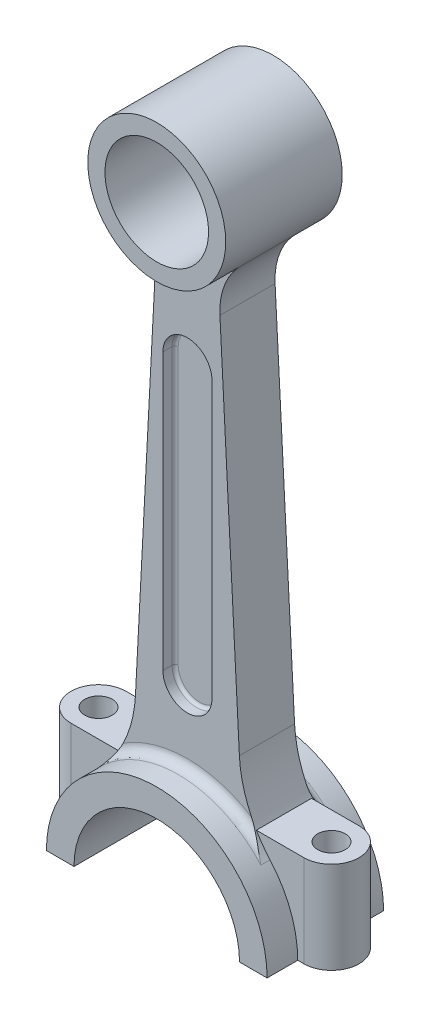
SolidWorks part; units mm, degrees
ref_plane "Front Plane" through (0, 0, 0) normal (0, 0, 1) x (1, 0, 0)
ref_plane "Top Plane" through (0, 0, 0) normal (0, 1, 0) x (1, 0, 0)
ref_plane "Right Plane" through (0, 0, 0) normal (1, 0, 0) x (0, 0, -1)
sketch "Sketch3" plane through (0, 0, 0) normal (0, 0, 1) x (1, 0, 0)
  line L0 (-10, -20.1556) -> (-17.8497, -169.9368)
  line L1 (10, -20.1556) -> (17.8497, -169.9368)
  line L2 (0, 0) -> (0, -201.2) construction
  line L3 (-36, -201.2) -> (-27, -201.2)
  line L4 (27, -201.2) -> (36, -201.2)
  circle A0 centre (0, 0) radius 22.5
  circle A1 centre (0, 0) radius 16.9
  arc A2 (36, -201.2) -> (-36, -201.2) centre (0, -201.2) ccw
  arc A3 (27, -201.2) -> (-27, -201.2) centre (0, -201.2) ccw
  dimension "D1" = 45
  dimension "D2" = 33.8
  dimension "D3" = 72
  dimension "D4" = 54
  dimension "D5" = 6
  dimension "D6" = 20
  dimension "D7" = 201.2
extrude "Boss-Extrude1" add sketch "Sketch3" along normal mid plane 38 contours A1 A0 region at (-11.5231, 18.5805, 0)
extrude "Boss-Extrude2" add sketch "Sketch3<3>" along normal mid plane 18 contours A0 L2 A2 L1 | L2 A0 L0 A2 region at (-7.1843, -100.8455, 0) region at (7.1843, -100.8455, 0)
sketch "Sketch3<3>" plane through (0, 0, 0) normal (0, 0, 1) x (1, 0, 0) same geometry as "Sketch3"
extrude "Boss-Extrude3" add sketch "Sketch3<5>" along normal mid plane 38 contours A2 L2 A3 L4 | L2 A2 L3 A3 region at (-20.1899, -181.0101, 0) region at (20.1899, -181.0101, 0)
sketch "Sketch3<5>" plane through (0, 0, 0) normal (0, 0, 1) x (1, 0, 0) same geometry as "Sketch3"
ref_plane "Plane2" through (0, -171.2, 0) normal (0, -1, 0) x (-1, 0, 0)
sketch "Sketch5" plane through (0, -171.2, 0) normal (0, -1, 0) x (-1, 0, 0)
  line L0 (38, 0) -> (-38, 0) construction
  line L1 (38, -9) -> (-38, -9)
  line L2 (38, 9) -> (-38, 9)
  arc A0 (38, -9) -> (38, 9) centre (38, 0) ccw
  arc A1 (-38, 9) -> (-38, -9) centre (-38, 0) ccw
  circle A2 centre (38, 0) radius 4.5
  circle A3 centre (-38, 0) radius 4.5
  point P2 (0, 0)
  dimension "D1" = 9
  dimension "D2" = 9
  dimension "D3" = 76
fillet "Fillet1" radius 40 2 edges at (17.8497, -169.9368, 0) (-17.8497, -169.9368, 0)
fillet "Fillet2" radius 22.5 2 edges at (10, -20.1556, 0) (-10, -20.1556, 0)
fillet "Fillet3" radius 3 2 edges at (0, -165.2, 9) (0, -165.2, -9)
extrude "Boss-Extrude5" add sketch "Sketch5" along normal blind 30
sketch "Sketch8" plane through (0, 0, -9) normal (0, 0, -1) x (-1, 0, 0)
  line L0 (-27, -201.2) -> (27, -201.2) construction
  line L1 (-36, -201.2) -> (-27, -201.2) construction
  line L2 (27, -201.2) -> (36, -201.2) construction
  line L3 (-27, -201.2) -> (27, -201.2)
  line L4 (-36, -201.2) -> (-27, -201.2)
  line L5 (27, -201.2) -> (36, -201.2)
  arc A0 (27, -201.2) -> (-27, -201.2) centre (0, -201.2) ccw construction
  arc A1 (36, -201.2) -> (-36, -201.2) centre (0, -201.2) ccw construction
  arc A2 (27, -201.2) -> (-27, -201.2) centre (0, -201.2) ccw construction
  arc A3 (27, -201.2) -> (-27, -201.2) centre (0, -201.2) ccw
  arc A4 (36, -201.2) -> (-36, -201.2) centre (0, -201.2) ccw
  arc A5 (27, -201.2) -> (-27, -201.2) centre (0, -201.2) ccw
  arc M3 (27, -201.2) -> (-27, -201.2) centre (0, -201.2) ccw
  line M4 (-27, -201.2) -> (27, -201.2)
extrude "Cut-Extrude2" cut sketch "Sketch8" against normal blind 30 contours M4 M3 region at (0, -189.7408, -9)
sketch "Sketch9" plane through (0, 0, -9) normal (0, 0, -1) x (-1, 0, 0)
  line L0 (-10, -20.1556) -> (-17.8497, -169.9368) construction
  line L1 (10, -20.1556) -> (17.8497, -169.9368) construction
  line L2 (27, -201.2) -> (36, -201.2)
  line L3 (-36, -201.2) -> (-27, -201.2)
  line L4 (27, -201.2) -> (36, -201.2)
  line L5 (-36, -201.2) -> (-27, -201.2)
  line L6 (-10, -20.1556) -> (-17.8497, -169.9368)
  line L7 (10, -20.1556) -> (17.8497, -169.9368)
  line L8 (0, 0) -> (0, -201.2) construction
  line L9 (0, -51.3069) -> (0, -141.3069) construction
  line L10 (8, -51.3069) -> (8, -141.3069)
  line L11 (-8, -51.3069) -> (-8, -141.3069)
  arc A0 (8, -51.3069) -> (-8, -51.3069) centre (0, -51.3069) ccw
  circle A1 centre (0, 0) radius 16.9
  circle A2 centre (0, 0) radius 16.9
  circle A3 centre (0, 0) radius 22.5
  circle A4 centre (0, 0) radius 22.5
  arc A5 (-8, -141.3069) -> (8, -141.3069) centre (0, -141.3069) ccw
  arc A6 (27, -201.2) -> (-27, -201.2) centre (0, -201.2) ccw
  arc A7 (36, -201.2) -> (-36, -201.2) centre (0, -201.2) ccw
  arc A8 (27, -201.2) -> (-27, -201.2) centre (0, -201.2) ccw
  arc A9 (36, -201.2) -> (-36, -201.2) centre (0, -201.2) ccw
  point P18 (0, -96.3069)
  dimension "D5" = 8
  dimension "D4" = 90
  dimension "D1" = 0
  dimension "D2" = 0
  dimension "D3" = 0
sketch "Sketch10" plane through (0, 0, 9) normal (0, 0, 1) x (1, 0, 0)
  line L0 (-10, -20.1556) -> (-17.8497, -169.9368) construction
  line L1 (10, -20.1556) -> (17.8497, -169.9368) construction
  line L2 (-36, -201.2) -> (-27, -201.2)
  line L3 (27, -201.2) -> (36, -201.2)
  line L4 (-36, -201.2) -> (-27, -201.2)
  line L5 (27, -201.2) -> (36, -201.2)
  line L6 (-8, -51.3069) -> (-8, -141.3069)
  line L7 (8, -141.3069) -> (8, -51.3069)
  line L8 (-8, -51.3069) -> (-8, -141.3069)
  line L9 (8, -141.3069) -> (8, -51.3069)
  line L10 (-10, -20.1556) -> (-17.8497, -169.9368)
  line L11 (10, -20.1556) -> (17.8497, -169.9368)
  circle A1 centre (0, 0) radius 22.5
  circle A2 centre (0, 0) radius 22.5
  circle A3 centre (0, 0) radius 16.9
  circle A4 centre (0, 0) radius 16.9
  arc A6 (36, -201.2) -> (-36, -201.2) centre (0, -201.2) ccw
  arc A7 (27, -201.2) -> (-27, -201.2) centre (0, -201.2) ccw
  arc A8 (36, -201.2) -> (-36, -201.2) centre (0, -201.2) ccw
  arc A9 (27, -201.2) -> (-27, -201.2) centre (0, -201.2) ccw
  arc A10 (-8, -141.3069) -> (8, -141.3069) centre (0, -141.3069) ccw
  arc A11 (8, -51.3069) -> (-8, -51.3069) centre (0, -51.3069) ccw
  arc A12 (-8, -141.3069) -> (8, -141.3069) centre (0, -141.3069) ccw
  arc A13 (8, -51.3069) -> (-8, -51.3069) centre (0, -51.3069) ccw
  dimension "D1" = 0
  dimension "D2" = 0
  dimension "D3" = 0
  dimension "D4" = 0
extrude "Cut-Extrude3" cut sketch "Sketch9" against normal blind 4 contours L11 A5 L10 A0 region at (0, -96.3069, -9)
extrude "Cut-Extrude4" cut sketch "Sketch10" against normal blind 4 contours L9 A13 L8 A12 region at (0, -96.3069, 9)
fillet "Fillet4" radius 1 8 edges at (0, -43.3069, -5) (-8, -96.3069, -5) (0, -149.3069, -5) (0, -149.3069, 5) (-8, -96.3069, 5) (0, -43.3069, 5) (8, -96.3069, 5) (8, -96.3069, -5)
